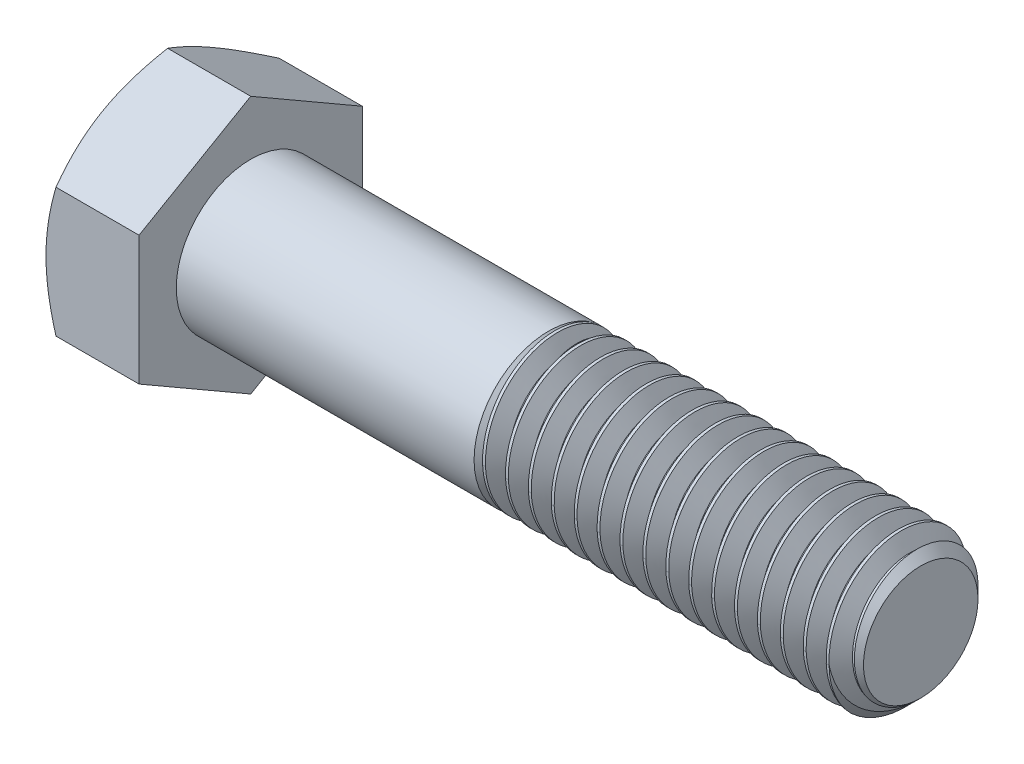
SolidWorks part; units mm, degrees
ref_plane "Front Plane" through (0, 0, 0) normal (0, 0, 1) x (1, 0, 0)
ref_plane "Top Plane" through (0, 0, 0) normal (0, 1, 0) x (1, 0, 0)
ref_plane "Right Plane" through (0, 0, 0) normal (1, 0, 0) x (0, 0, -1)
sketch "Sketch1" plane through (0, 0, 0) normal (0, 0, 1) x (1, 0, 0)
  line L0 (-32.5437, 0) -> (32.5437, 0) construction
  line L1 (32.5437, 6.35) -> (32.5437, -6.35) construction
  line L2 (-24.6063, 9.525) -> (-24.6063, -9.525) construction
  line L3 (-32.5437, 9.525) -> (-32.5437, -9.525) construction
  point P9 (-24.6062, 0)
  point P10 (25.7053, -6.35)
  dimension "Screw Dia" = 12.7
  dimension "Hex" = 19.05
  dimension "Head Ht" = 7.9375
  dimension "Screw Lenght" = 57.15
  dimension "D1" = 6.8385
ref_plane "Plane2" through (32.5437, 0, 0) normal (1, 0, 0) x (0, 0, -1)
sketch "Sketch5" plane through (32.5437, 0, 0) normal (1, 0, 0) x (0, 0, -1)
  circle A0 centre (0, 0) radius 6.35
extrude "Boss-Extrude3" add sketch "Sketch5" against normal up to vertex (57.15 mm away) up to point (-24.6062, 0, 0)
sketch "Sketch9" plane through (32.5437, 0, 0) normal (1, 0, 0) x (0, 0, -1)
  circle A1 centre (0, 0) radius 6.35
  circle A2 centre (0, 0) radius 6.35
  dimension "D1" = 0
curve "Helix/Spiral1" pitch 1.9538 height 33.7038 turns 17.25 parameters "Pitch"=1.9538
chamfer "Chamfer1" distance 1.4654 angle 45 1 edges at (32.5437, 0, -6.35)
sketch "Sketch10" plane through (0, 0, 0) normal (0, 0, 1) x (1, 0, 0)
  line L0 (32.5437, 6.35) -> (33.2764, 5.0809)
  line L1 (33.2764, 5.0809) -> (33.5207, 5.0809)
  line L2 (33.5207, 5.0809) -> (34.2534, 6.35)
  line L3 (32.5437, 6.35) -> (34.2534, 6.35)
  line L4 (33.3986, 6.35) -> (33.3986, 5.0809) construction
  line L5 (32.9101, 5.7155) -> (33.887, 5.7155) construction
  dimension "D1" = 60
  dimension "D2" = 0.2442
  dimension "D3" = 0.9769
sweep "Cut-Sweep1" cut profiles "Sketch10" path "Helix/Spiral1" align with end faces yes
sketch "Sketch11" plane through (0, 0, 0) normal (0, 0, 1) x (1, 0, 0)
  line L0 (-24.6063, 6.35) -> (-24.6062, 0)
  line L1 (-24.6062, 0) -> (7.1438, 0)
  line L3 (7.1438, 0) -> (0.7937, 6.35)
  line L4 (-24.6063, 6.35) -> (0.7937, 6.35)
  dimension "D1" = 45
  dimension "MIn Thread" = 31.75
revolve "Revolve1" add sketch "Sketch11" angle 360 about L1
sketch "Sketch6" plane through (-24.6062, 0, 0) normal (-1, 0, 0) x (0, 0, 1)
  line L0 (0, 9.525) -> (0, -9.525) construction
  line L1 (9.525, 5.4993) -> (0, 10.9985)
  line L2 (0, 10.9985) -> (-9.525, 5.4993)
  line L3 (-9.525, 5.4993) -> (-9.525, -5.4993)
  line L4 (-9.525, -5.4993) -> (0, -10.9985)
  line L5 (0, -10.9985) -> (9.525, -5.4993)
  line L6 (9.525, -5.4993) -> (9.525, 5.4993)
  circle A0 centre (0, 0) radius 9.525 construction
extrude "Boss-Extrude4" add sketch "Sketch6" along normal up to vertex
sketch "Sketch7" plane through (-32.5437, 0, 0) normal (-1, 0, 0) x (0, 0, 1)
  circle A0 centre (0, 0) radius 9.525 construction
  circle A1 centre (0, 0) radius 9.525
sketch "Sketch8" plane through (-32.5437, 0, 0) normal (-1, 0, 0) x (0, 0, 1)
  circle A0 centre (0, 0) radius 9.525 construction
  circle A1 centre (0, 0) radius 9.525
extrude "Cut-Extrude3" cut sketch "Sketch8" against normal through all draft 60 flip side to cut
sketch "Sketch12" plane through (-32.5437, 0, 0) normal (-1, 0, 0) x (0, 0, 1)
  line L0 (0, 7.3343) -> (0, 4.0958) construction
  line L1 (0.2858, 7.3343) -> (0.2858, 4.0958)
  line L2 (-0.2858, 7.3343) -> (-0.2857, 4.0958)
  line L3 (0, 6.35) -> (0, -6.35) construction
  arc A0 (0.2858, 7.3343) -> (-0.2858, 7.3343) centre (0, 7.3343) ccw
  arc A1 (-0.2857, 4.0958) -> (0.2858, 4.0958) centre (0, 4.0958) ccw
  circle A3 centre (0, 0) radius 3.81 construction
  circle A4 centre (0, 0) radius 7.62 construction
  point P2 (0, 5.715)
  dimension "D1" = 7.62
  dimension "D3" = 15.24
  dimension "D2" = 0.5715
extrude "Cut-Extrude4" cut sketch "Sketch12" against normal blind 0.254
pattern_circular "CirPattern1" count 3 over 360 about axis through (0, 0, 0) along (1, 0, 0) of "Cut-Extrude4"
equation "\"D2@Sketch10\" = \"Pitch@Helix/Spiral1\"*.125"
equation "\"D3@Sketch10\" = \"Pitch@Helix/Spiral1\"*.5"
equation "\"D3@Helix/Spiral1\" = \"MIn Thread@Sketch11\"+\"Pitch@Helix/Spiral1\""
equation "\"D1@Chamfer1\" = \"Pitch@Helix/Spiral1\"*.75"
equation "\"D1@Sketch12\" = \"Hex@Sketch1\"*.4"
equation "\"D3@Sketch12\" = \"Hex@Sketch1\"*.8"
equation "\"D2@Sketch12\" = \"Hex@Sketch1\"*.03"
equation "\"D1@Sketch1\" = \"Pitch@Helix/Spiral1\"*3.5"
